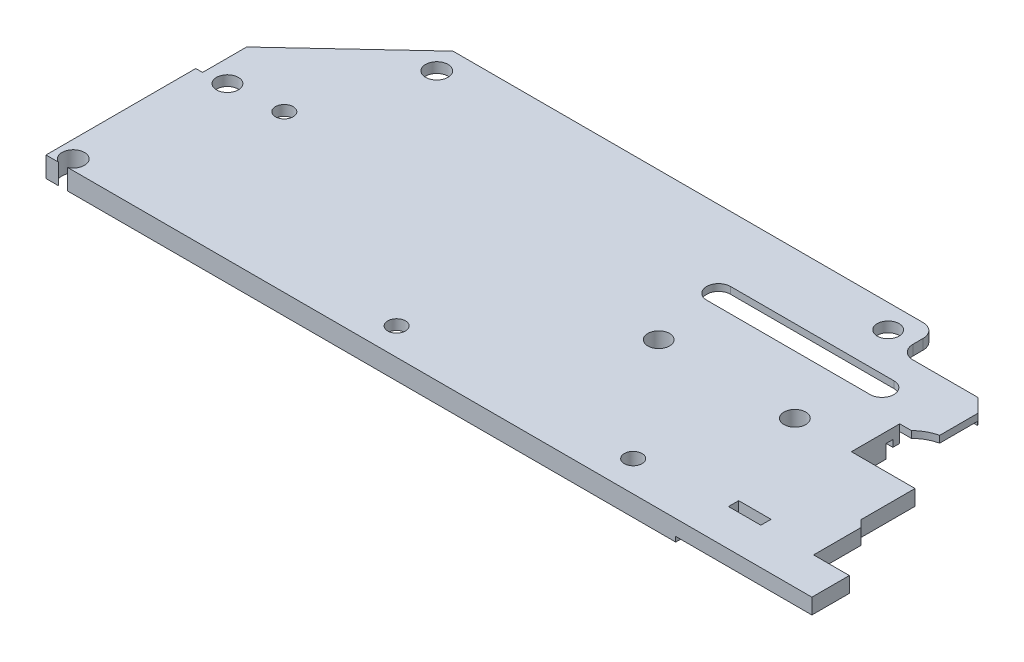
SolidWorks part; units mm, degrees
ref_plane "前视基准面" through (0, 0, 0) normal (0, 0, 1) x (1, 0, 0)
ref_plane "上视基准面" through (0, 0, 0) normal (0, 1, 0) x (1, 0, 0)
ref_plane "右视基准面" through (0, 0, 0) normal (1, 0, 0) x (0, 0, -1)
other "Configuration Table"
sketch "草图1" plane through (0, 0, 0) normal (0, 1, 0) x (1, 0, 0)
  line L0 (0, 0) -> (20, 0) construction
  line L2 (-3, 5) -> (27.5, 5)
  line L3 (-3, 5) -> (-3, -3.5)
  line L4 (-3, -3.5) -> (27.5, -3.5)
  line L5 (27.5, 5) -> (27.5, -3.5)
  line L6 (-3, 5) -> (27.5, -3.5) construction
  line L7 (-3, -3.5) -> (27.5, 5) construction
  circle A0 centre (0, 0) radius 1.6
  circle A1 centre (20, 0) radius 1.6
  point P9 (12.25, 0.75)
  dimension "D1" = 20
  dimension "D2" = 3.2
  dimension "D3" = 3
  dimension "D4" = 3.5
  dimension "D5" = 5
  dimension "D6" = 30.5
extrude "凸台-拉伸1" add sketch "草图1" along normal blind 3.5
sketch "草图2" plane through (0, 3.5, 0) normal (0, 1, 0) x (1, 0, 0)
  line L1 (-3, -3.5) -> (27.5, -3.5)
  line L2 (-3, -3.5) -> (-3, -21.5)
  line L3 (-3, -21.5) -> (27.5, -21.5)
  line L4 (27.5, -3.5) -> (27.5, -21.5)
  line L5 (-3, -3.5) -> (27.5, -21.5) construction
  line L6 (-3, -21.5) -> (27.5, -3.5) construction
  point P4 (12.25, -12.5)
  dimension "D1" = 18
extrude "凸台-拉伸2" add sketch "草图2" against normal blind 3
sketch "草图3" plane through (0, 3.5, 0) normal (0, 1, 0) x (1, 0, 0)
  line L1 (-3, 5) -> (27.5, 5)
  line L2 (-3, 5) -> (-3, 21.6)
  line L3 (-3, 21.6) -> (27.5, 21.6)
  line L4 (27.5, 5) -> (27.5, 21.6)
  line L5 (-3, 5) -> (27.5, 21.6) construction
  line L6 (-3, 21.6) -> (27.5, 5) construction
  point P4 (12.25, 13.3)
  dimension "D1" = 16.6
extrude "凸台-拉伸3" add sketch "草图3" against normal blind 1.5
sketch "草图4" plane through (-3, 0, 0) normal (-1, 0, 0) x (0, 0, 1)
  line L0 (3.5, 0.5) -> (-5, 0.5)
  line L1 (3.5, 0.5) -> (3.5, 0) construction
  line L2 (-5, 2) -> (-5, 0) construction
  line L3 (-5, 0.5) -> (-5, 2)
  line L8 (-5, 0) -> (3.5, 0)
  line L9 (3.5, 0) -> (3.5, 0.5)
  line L10 (3.5, 0.5) -> (21.5, 0.5)
  line L11 (21.5, 0.5) -> (21.5, 3.5)
  line L12 (21.5, 3.5) -> (-21.6, 3.5)
  line L13 (-21.6, 3.5) -> (-21.6, 2)
  line L14 (-21.6, 2) -> (-5, 2)
  line L15 (-5, 2) -> (-5, 0)
  line L18 (3.5, 0.5) -> (21.5, 0.5)
  line L19 (21.5, 0.5) -> (21.5, 3.5)
  line L20 (21.5, 3.5) -> (-21.6, 3.5)
  line L21 (-21.6, 3.5) -> (-21.6, 2)
  line L22 (-21.6, 2) -> (-5, 2)
  dimension "D1" = 0
extrude "凸台-拉伸4" add sketch "草图4" along normal blind 57
sketch "草图5" plane through (-60, 0, 0) normal (-1, 0, 0) x (0, 0, 1)
  line L1 (-21.6, 2) -> (21.5, 2)
  line L2 (-21.6, 2) -> (-21.6, 3.5)
  line L3 (-21.6, 3.5) -> (21.5, 3.5)
  line L4 (21.5, 2) -> (21.5, 3.5)
  line L5 (-21.6, 2) -> (21.5, 3.5) construction
  line L6 (-21.6, 3.5) -> (21.5, 2) construction
  point P4 (-0.05, 2.75)
extrude "凸台-拉伸5" add sketch "草图5" along normal blind 2.5
sketch "草图6" plane through (0, 3.5, 0) normal (0, 1, 0) x (1, 0, 0)
  line L0 (-53.5761, 21.6) -> (-62.5, 13.2783)
  line L1 (-62.5, -21.5) -> (-62.5, 21.6) construction
  line L2 (-62.5, 13.2783) -> (-62.5, 21.6)
  line L3 (-62.5, 21.6) -> (-53.5761, 21.6)
  line L7 (27.5, 21.6) -> (-62.5, 21.6) construction
  dimension "D1" = 8.9239
  dimension "D2" = 8.3217
extrude "切除-拉伸1" cut sketch "草图6" against normal through all
sketch "草图7" plane through (0, 0.5, 0) normal (0, -1, 0) x (1, 0, 0)
  line L0 (-3, -5) -> (-3, 3.5) construction
  line L1 (-60, -5) -> (-3, -5)
  line L2 (-60, -5) -> (-60, -4)
  line L3 (-60, -4) -> (-3, -4)
  line L4 (-3, -5) -> (-3, -4)
  line L5 (-60, -5) -> (-3, -4) construction
  line L6 (-60, -4) -> (-3, -5) construction
  point P4 (-31.5, -4.5)
  dimension "D1" = 1
extrude "切除-拉伸2" cut sketch "草图7" against normal up to surface (1.5 mm away) up to face at (-34.7966, 2, -3.354)
sketch "草图8" plane through (27.5, 0, 0) normal (1, 0, 0) x (0, 0, -1)
  line L1 (-3.5, 0.5) -> (-21.5, 0.5)
  line L2 (-3.5, 0.5) -> (-3.5, 3.5)
  line L3 (-3.5, 3.5) -> (-21.5, 3.5)
  line L4 (-21.5, 0.5) -> (-21.5, 3.5)
  line L5 (-3.5, 0.5) -> (-21.5, 3.5) construction
  line L6 (-3.5, 3.5) -> (-21.5, 0.5) construction
  point P4 (-12.5, 2)
extrude "凸台-拉伸6" add sketch "草图8" along normal blind 16.5
sketch "草图9" plane through (0, 0.5, 0) normal (0, -1, 0) x (1, 0, 0)
  line L1 (44, 21.5) -> (24, 21.5)
  line L2 (44, 21.5) -> (44, 11.1)
  line L3 (44, 11.1) -> (24, 11.1)
  line L4 (24, 21.5) -> (24, 11.1)
  line L5 (44, 21.5) -> (24, 11.1) construction
  line L6 (44, 11.1) -> (24, 21.5) construction
  point P4 (34, 16.3)
  dimension "D1" = 20
  dimension "D2" = 10.4
extrude "切除-拉伸3" cut sketch "草图9" against normal blind 0.725 contours L4 L3 L2 L1
sketch "草图10" plane through (0, 1.225, 0) normal (0, -1, 0) x (1, 0, 0)
  line L0 (44, 21.5) -> (24, 21.5) construction
  line L1 (26.35, 16.1) -> (31.1, 16.1)
  line L2 (26.35, 16.1) -> (26.35, 14.6)
  line L3 (26.35, 14.6) -> (31.1, 14.6)
  line L4 (31.1, 16.1) -> (31.1, 14.6)
  line L5 (26.35, 16.1) -> (31.1, 14.6) construction
  line L6 (26.35, 14.6) -> (31.1, 16.1) construction
  line L8 (44, 21.5) -> (44, 11.1) construction
  point P4 (28.725, 15.35)
  dimension "D1" = 4.75
  dimension "D2" = 1.5
  dimension "D3" = 5.4
  dimension "D4" = 17.65
extrude "切除-拉伸4" cut sketch "草图10" against normal up to next
sketch "草图11" plane through (0, 0.5, 0) normal (0, -1, 0) x (1, 0, 0)
  line L0 (44, 11.1) -> (24, 11.1) construction
  line L1 (44, 3.5) -> (29, 3.5)
  line L2 (44, 3.5) -> (44, 11.1)
  line L3 (44, 11.1) -> (29, 11.1)
  line L4 (29, 3.5) -> (29, 11.1)
  line L5 (44, 3.5) -> (29, 11.1) construction
  line L6 (44, 11.1) -> (29, 3.5) construction
  line L7 (24, 21.5) -> (24, 11.1) construction
  point P4 (36.5, 7.3)
  dimension "D1" = 5
extrude "切除-拉伸5" cut sketch "草图11" against normal up to surface (0.725 mm away) up to face at (28.725, 1.225, 15.35)
sketch "草图12" plane through (27.5, 0, 0) normal (1, 0, 0) x (0, 0, -1)
  line L1 (5, 0) -> (-3.5, 0)
  line L2 (5, 0) -> (5, 3.5)
  line L3 (5, 3.5) -> (-3.5, 3.5)
  line L4 (-3.5, 0) -> (-3.5, 3.5)
  line L5 (5, 0) -> (-3.5, 3.5) construction
  line L6 (5, 3.5) -> (-3.5, 0) construction
  point P4 (0.75, 1.75)
extrude "凸台-拉伸7" add sketch "草图12" along normal up to surface (1.5 mm away) up to face at (29, 0.8625, 7.3)
sketch "草图13" plane through (0, 0, 0) normal (0, -1, 0) x (1, 0, 0)
  line L0 (27.5, -5) -> (29, 3.5)
  line L1 (29, 3.5) -> (29, -5)
  line L2 (29, -5) -> (27.5, -5)
extrude "切除-拉伸6" cut sketch "草图13" against normal up to next
sketch "草图14" plane through (0, 3.5, 0) normal (0, 1, 0) x (1, 0, 0)
  line L0 (28.4, -0.1) -> (29, -3.5)
  line L1 (29, -3.5) -> (27.5, 5) construction
  line L2 (29, -3.5) -> (33.5, -3.5)
  line L3 (44, -3.5) -> (29, -3.5) construction
  line L4 (33.5, -3.5) -> (33.5, -0.1)
  line L5 (33.5, -0.1) -> (28.4, -0.1)
  line L6 (44, -3.5) -> (44, -21.5) construction
  dimension "D1" = 10.5
  dimension "D2" = 3.4
extrude "凸台-拉伸8" add sketch "草图14" against normal up to surface (3.5 mm away) up to face at (12.625, 0, -0.75)
sketch "草图15" plane through (0, 3.5, 0) normal (0, 1, 0) x (1, 0, 0)
  line L0 (44, -3.5) -> (44, -21.5) construction
  line L1 (33.5, -3.5) -> (40.5, -3.5)
  line L2 (33.5, -3.5) -> (33.5, -0.1)
  line L3 (33.5, -0.1) -> (40.5, -0.1)
  line L4 (40.5, -3.5) -> (40.5, -0.1)
  line L5 (33.5, -3.5) -> (40.5, -0.1) construction
  line L6 (33.5, -0.1) -> (40.5, -3.5) construction
  point P4 (37, -1.8)
  dimension "D1" = 3.5
extrude "凸台-拉伸9" add sketch "草图15" against normal up to surface (2.275 mm away) up to face at (28.725, 1.225, 15.35)
sketch "草图16" plane through (0, 3.5, 0) normal (0, 1, 0) x (1, 0, 0)
  line L0 (40.5, -3.5) -> (40.5, -0.1) construction
  line L1 (44, -3.5) -> (40.5, -3.5)
  line L2 (44, -3.5) -> (44, -2)
  line L3 (44, -2) -> (40.5, -2)
  line L4 (40.5, -3.5) -> (40.5, -2)
  line L5 (44, -3.5) -> (40.5, -2) construction
  line L6 (44, -2) -> (40.5, -3.5) construction
  point P4 (42.25, -2.75)
  dimension "D1" = 1.5
extrude "凸台-拉伸10" add sketch "草图16" against normal up to surface (2.275 mm away) up to face at (28.725, 1.225, 15.35)
sketch "草图17" plane through (0, 1.225, 0) normal (0, -1, 0) x (1, 0, 0)
  line L0 (44, 21.5) -> (44, 2) construction
  line L1 (44, 16) -> (38.75, 16)
  line L2 (44, 16) -> (44, 0.1)
  line L3 (44, 0.1) -> (38.75, 0.1)
  line L4 (38.75, 16) -> (38.75, 0.1)
  line L5 (44, 16) -> (38.75, 0.1) construction
  line L6 (44, 0.1) -> (38.75, 16) construction
  line L7 (44, 21.5) -> (24, 21.5) construction
  line L8 (40.5, 0.1) -> (33.5, 0.1) construction
  point P4 (41.375, 8.05)
  dimension "D1" = 5.25
  dimension "D2" = 5.5
extrude "切除-拉伸7" cut sketch "草图17" against normal up to next
sketch "草图18" plane through (0, 0.5, 0) normal (0, -1, 0) x (1, 0, 0)
  line L0 (24, 11.1) -> (29, 6.1)
  line L1 (29, 11.1) -> (29, 3.5) construction
  line L2 (29, 6.1) -> (29, 11.1)
  line L3 (29, 11.1) -> (24, 11.1)
extrude "切除-拉伸8" cut sketch "草图18" against normal up to surface (0.725 mm away) up to face at (33.85, 1.225, 10.44)
sketch "草图19" plane through (0, 1.225, 0) normal (0, -1, 0) x (1, 0, 0)
  line L0 (38.75, 9) -> (37.75, 9)
  line L1 (38.75, 16) -> (38.75, 0.1) construction
  line L2 (37.75, 9) -> (37.75, 0.1)
  line L3 (38.75, 0.1) -> (33.5, 0.1) construction
  line L4 (37.75, 0.1) -> (38.75, 0.1)
  line L5 (38.75, 0.1) -> (38.75, 9)
  line L6 (44, 16) -> (38.75, 16) construction
  dimension "D1" = 1
  dimension "D2" = 7
extrude "切除-拉伸9" cut sketch "草图19" against normal up to next
chamfer "倒角1" distance 1 angle 45 1 edges at (37.75, 2.3625, 9)
sketch "草图20" plane through (0, 3.5, 0) normal (0, 1, 0) x (1, 0, 0)
  line L0 (-1.5, 10.3) -> (22.5, 10.3) construction
  line L1 (-1.5, 12.05) -> (22.5, 12.05)
  line L2 (-1.5, 8.55) -> (22.5, 8.55)
  line L3 (27.5, 21.6) -> (-53.5761, 21.6) construction
  line L4 (27.5, 5) -> (27.5, 21.6) construction
  arc A0 (-1.5, 12.05) -> (-1.5, 8.55) centre (-1.5, 10.3) ccw
  arc A1 (22.5, 8.55) -> (22.5, 12.05) centre (22.5, 10.3) ccw
  point P2 (10.5, 10.3)
  dimension "D4" = 1.75
  dimension "D1" = 11.3
  dimension "D2" = 24
  dimension "D3" = 17
extrude "切除-拉伸10" cut sketch "草图20" against normal up to next
sketch "草图22" plane through (0, 2, 0) normal (0, -1, 0) x (1, 0, 0)
  line L2 (-51.1362, -18.4059) -> (16.75, -18.4059)
  line L3 (27.5, -5) -> (27.5, -21.6) construction
  line L4 (16.75, -18.4059) -> (16.75, -19.4059)
  line L7 (-59, -6) -> (27.5, -6)
  line L8 (-52.6024, -18.4059) -> (-60, -11.5076)
  line L9 (-51.5301, -19.4059) -> (-60.454, -11.0842)
  line L11 (-51.5301, -19.4059) -> (-52.6024, -18.4059)
  line L14 (16.75, -19.4059) -> (-51.5301, -19.4059)
  line L15 (-60, -11.5076) -> (-60, -6)
  line L16 (-60, -6) -> (-59, -6)
  line L17 (-59, -7) -> (-59, -11.0728)
  line L18 (-59, -11.0728) -> (-51.1362, -18.4059)
  line L20 (-60, -4) -> (-60, 21.5) construction
  line L21 (-60, -4) -> (-3, -4) construction
  line L22 (-59, -7) -> (27.5, -7)
  line L23 (27.5, -6) -> (27.5, -7)
  line L24 (-59, -6) -> (27.5, -7) construction
  line L25 (-59, -7) -> (27.5, -6) construction
  point P19 (-15.75, -6.5)
  dimension "D2" = 1
  dimension "D3" = 1
  dimension "D4" = 2
  dimension "D5" = 1
  dimension "D6" = 1
  dimension "D7" = 10.75
  dimension "D1" = 3
extrude "凸台-拉伸12" add sketch "草图22" along normal blind 1
sketch "草图23" plane through (0, 3.5, 0) normal (0, 1, 0) x (1, 0, 0)
  line L0 (-62.5, -21.5) -> (-62.5, 13.2783) construction
  line L1 (-62.5, -21.5) -> (44, -21.5) construction
  line L2 (-62.5, 13.2783) -> (-67.5, 8.6157)
  line L3 (-67.5, 8.6157) -> (-67.5, -21.5)
  line L4 (-67.5, -21.5) -> (-62.5, -21.5)
  line L5 (-62.5, -21.5) -> (-62.5, 13.2783)
  line L6 (-62.5, 13.2783) -> (-53.5761, 21.6) construction
  circle A0 centre (-64.25, 0.9) radius 1.6
  dimension "D1" = 1.75
  dimension "D3" = 3.2
  dimension "D2" = 22.4
  dimension "D4" = 5
extrude "凸台-拉伸13" add sketch "草图23" against normal up to surface (1.5 mm away) up to face at (10.5, 2, -10.3)
sketch "草图24" plane through (0, 2, 0) normal (0, -1, 0) x (1, 0, 0)
  line L0 (-67.5, -8.6157) -> (-67.5, 21.5) construction
  line L1 (-60, 21.5) -> (-67.5, 21.5)
  line L2 (-60, 21.5) -> (-60, 4.5)
  line L3 (-60, 4.5) -> (-67.5, 4.5)
  line L4 (-67.5, 21.5) -> (-67.5, 4.5)
  line L5 (-60, 21.5) -> (-67.5, 4.5) construction
  line L6 (-60, 4.5) -> (-67.5, 21.5) construction
  point P4 (-63.75, 13)
  dimension "D1" = 17
extrude "凸台-拉伸14" add sketch "草图24" along normal up to surface (1.5 mm away) up to face at (-2.5, 0.5, 7.4)
chamfer "倒角2" distance 4.5 angle 37.5 1 edges at (-60, 1.25, 4.5)
sketch "草图25" plane through (0, 3.5, 0) normal (0, 1, 0) x (1, 0, 0)
  line L0 (27.5, 21.6) -> (-53.5761, 21.6) construction
  line L1 (-67.5, 8.6157) -> (-67.5, -21.5) construction
  circle A0 centre (-50.5, 17.9) radius 1.65
  dimension "D1" = 3.3
  dimension "D2" = 3.7
  dimension "D3" = 17
extrude "切除-拉伸11" cut sketch "草图25" against normal up to next
sketch "草图26" plane through (0, 2, 0) normal (0, -1, 0) x (1, 0, 0)
  circle A0 centre (-50.5, -17.9) radius 4
  dimension "D1" = 8
extrude "切除-拉伸12" cut sketch "草图26" along normal up to next
fillet "圆角1" radius 1 2 edges at (-46.7943, 1.5, -19.4059) (-54.3413, 1.5, -16.7844)
sketch "草图27" plane through (0, 2, 0) normal (0, -1, 0) x (1, 0, 0)
  line L0 (-53.914, -15.8156) -> (-54.6574, -15.1223)
  line L1 (-53.914, -15.8156) -> (-59, -11.0728) construction
  line L2 (-45.5257, -18.4059) -> (-46.5321, -18.4059)
  line L3 (16.75, -18.4059) -> (-46.5321, -18.4059) construction
  arc A0 (-46.5321, -18.4059) -> (-53.914, -15.8156) centre (-50.5, -17.9) ccw
  arc A1 (-45.5257, -18.4059) -> (-54.6574, -15.1223) centre (-50.5, -17.9) ccw
  dimension "D1" = 1
extrude "凸台-拉伸15" add sketch "草图27" along normal up to surface (1 mm away) up to face at (-36.5289, 1, -10.0692)
fillet "圆角2" radius 1 4 edges at (-60, 1.5, -11.5076) (-59, 1.5, -11.0728) (-45.5257, 1.5, -18.4059) (-54.6574, 1.5, -15.1223)
fillet "圆角3" radius 1 3 edges at (-60, 1.25, -4) (-60, 1.5, -6) (-59, 1.5, -7)
sketch "草图28" plane through (0, 2, 0) normal (0, -1, 0) x (1, 0, 0)
  line L1 (27.5, -21.6) -> (20.5, -21.6)
  line L2 (27.5, -21.6) -> (27.5, -17.4)
  line L3 (27.5, -17.4) -> (20.5, -17.4)
  line L4 (20.5, -21.6) -> (20.5, -17.4)
  line L5 (27.5, -21.6) -> (20.5, -17.4) construction
  line L6 (27.5, -17.4) -> (20.5, -21.6) construction
  point P4 (24, -19.5)
  dimension "D1" = 4.2
  dimension "D2" = 7
extrude "切除-拉伸13" cut sketch "草图28" against normal up to next
sketch "草图29" plane through (0, 2, 0) normal (0, -1, 0) x (1, 0, 0)
  line L0 (20.5, -21.6) -> (19.25, -21.6)
  line L1 (20.5, -21.6) -> (-53.5761, -21.6) construction
  line L2 (19.25, -21.6) -> (19.25, -16.1)
  line L3 (19.25, -16.1) -> (27.5, -16.1)
  line L4 (27.5, -7) -> (27.5, -17.4) construction
  line L5 (27.5, -16.1) -> (27.5, -17.4)
  line L6 (27.5, -17.4) -> (20.5, -17.4) construction
  line L7 (27.5, -17.4) -> (20.5, -17.4)
  line L8 (20.5, -17.4) -> (20.5, -21.6)
  dimension "D1" = 1.3
  dimension "D2" = 1.25
extrude "凸台-拉伸16" add sketch "草图29" along normal up to surface (1 mm away) up to face at (-39.2289, 1, -12.6385)
fillet "圆角4" radius 2 2 edges at (19.25, 1.5, -16.1) (20.5, 2.25, -17.4)
sketch "草图30" plane through (0, 2, 0) normal (0, -1, 0) x (1, 0, 0)
  line L0 (19.25, -21.6) -> (-53.5761, -21.6) construction
  line L1 (27.5, -7) -> (27.5, -16.1) construction
  circle A0 centre (15.6, -18.1) radius 1.6
  dimension "D1" = 3.2
  dimension "D2" = 3.5
  dimension "D3" = 11.9
extrude "切除-拉伸14" cut sketch "草图30" against normal up to next
sketch "草图31" plane through (0, 2, 0) normal (0, -1, 0) x (1, 0, 0)
  circle A0 centre (15.6, -18.1) radius 3.75
  dimension "D1" = 7.5
extrude "切除-拉伸15" cut sketch "草图31" along normal up to next
fillet "圆角5" radius 1 1 edges at (12.0847, 1.5, -19.4059)
sketch "草图32" plane through (0, 1, 0) normal (0, -1, 0) x (1, 0, 0)
  line L1 (19.25, -18.9602) -> (19.25, -18.1)
  line L5 (19.25, -18.9602) -> (19.25, -21.6)
  line L6 (20.5, -21.6) -> (20.5, -19.4)
  line L7 (22.5, -17.4) -> (27.5, -17.4)
  line L8 (27.5, -17.4) -> (27.5, -16.1)
  line L9 (27.5, -16.1) -> (21.25, -16.1)
  line L10 (19.25, -18.9602) -> (19.25, -21.6)
  line L11 (20.5, -21.6) -> (20.5, -19.4)
  line L12 (22.5, -17.4) -> (27.5, -17.4)
  line L13 (27.5, -17.4) -> (27.5, -16.1)
  line L14 (27.5, -16.1) -> (21.25, -16.1)
  line L16 (19.25, -21.6) -> (20.5, -21.6)
  line L17 (19.25, -21.6) -> (20.5, -21.6)
  arc A3 (19.25, -18.9602) -> (19.3155, -17.5924) centre (15.6, -18.1) ccw
  arc A4 (22.5, -17.4) -> (20.5, -19.4) centre (22.5, -19.4) ccw
  arc A5 (21.25, -16.1) -> (19.3155, -17.5924) centre (21.25, -18.1) ccw
  arc A7 (22.5, -17.4) -> (20.5, -19.4) centre (22.5, -19.4) ccw
  arc A8 (21.25, -16.1) -> (19.25, -18.1) centre (21.25, -18.1) ccw
  dimension "D1" = 0
extrude "切除-拉伸16" cut sketch "草图32" against normal up to next
fillet "圆角7" radius 2 1 edges at (19.25, 2.75, -21.6)
sketch "草图33" plane through (0, 0, 0) normal (0, -1, 0) x (1, 0, 0)
  line L0 (28.4, 0.1) -> (27.5, -5)
  line L1 (27.5, -5) -> (28.4, -5)
  line L2 (28.4, -5) -> (28.4, 0.1)
extrude "凸台-拉伸17" add sketch "草图33" against normal up to surface (3.5 mm away) up to face at (13.3015, 3.5, -2.1572)
sketch "草图34" plane through (27.5, 0, 0) normal (1, 0, 0) x (0, 0, -1)
  line L8 (7, 2) -> (16.1, 2)
  line L9 (16.1, 2) -> (16.1, 3.5)
  line L10 (16.1, 3.5) -> (5, 3.5)
  line L11 (5, 3.5) -> (5, 2)
  line L12 (5, 2) -> (6, 2)
  line L13 (6, 2) -> (6, 1)
  line L14 (6, 1) -> (7, 1)
  line L15 (7, 1) -> (7, 2)
  line L16 (7, 2) -> (16.1, 2)
  line L17 (16.1, 2) -> (16.1, 3.5)
  line L18 (16.1, 3.5) -> (5, 3.5)
  line L19 (5, 3.5) -> (5, 2)
  line L20 (5, 2) -> (6, 2)
  line L21 (6, 2) -> (6, 1)
  line L22 (6, 1) -> (7, 1)
  line L23 (7, 1) -> (7, 2)
  dimension "D1" = 0
extrude "凸台-拉伸18" add sketch "草图34" along normal up to surface (0.9 mm away) up to face at (28.4, 1.75, -2.45)
sketch "草图35" plane through (0, 2, 0) normal (0, -1, 0) x (1, 0, 0)
  line L1 (28.4, -7) -> (-8.6, -7)
  line L2 (28.4, -7) -> (28.4, -14)
  line L3 (28.4, -14) -> (-8.6, -14)
  line L4 (-8.6, -7) -> (-8.6, -14)
  line L5 (28.4, -7) -> (-8.6, -14) construction
  line L6 (28.4, -14) -> (-8.6, -7) construction
  point P4 (9.9, -10.5)
  dimension "D1" = 7
  dimension "D2" = 37
extrude "切除-拉伸17" cut sketch "草图35" against normal blind 0.5
chamfer "倒角3" distance 0.5 angle 45 1 edges at (-8.6, 2, -10.5)
sketch "草图36" plane through (28.4, 0, 0) normal (1, 0, 0) x (0, 0, -1)
  line L0 (16.1, 2) -> (16.1, 3.5)
  line L1 (16.1, 3.5) -> (7, 3.5)
  line L2 (16.1, 3.5) -> (-0.1, 3.5) construction
  line L3 (7, 3.5) -> (7, 2.5)
  line L4 (14, 2.5) -> (7, 2.5) construction
  line L5 (7, 2.5) -> (14, 2.5)
  line L6 (14, 2.5) -> (14, 2)
  line L7 (14, 2) -> (16.1, 2)
extrude "凸台-拉伸19" add sketch "草图36" along normal blind 4.4
sketch "草图37" plane through (0, 3.5, 0) normal (0, 1, 0) x (1, 0, 0)
  line L0 (32.8, 16.1) -> (21.25, 16.1) construction
  line L1 (32.8, 16.1) -> (32.8, 7) construction
  line L2 (32.8, 7) -> (28.4, 7) construction
  line L3 (30.1219, 7) -> (32.8, 7)
  line L4 (32.8, 7) -> (32.8, 8.4675)
  arc A3 (32.8, 8.4675) -> (30.1219, 7) centre (34, 3.1) ccw
  dimension "D1" = 13
  dimension "D2" = 1.2
  dimension "D3" = 5.5
extrude "切除-拉伸18" cut sketch "草图37" against normal through all
sketch "草图38" plane through (0, 3.5, 0) normal (0, 1, 0) x (1, 0, 0)
  circle A0 centre (13.25, -17) radius 1.3
  circle A1 centre (20, 0) radius 1.6 construction
  dimension "D1" = 17
  dimension "D2" = 6.75
  dimension "D3" = 2.6
extrude "切除-拉伸19" cut sketch "草图38" against normal up to next
sketch "草图39" plane through (0, 2, 0) normal (0, -1, 0) x (1, 0, 0)
  line L0 (-67.5, 21.5) -> (24, 21.5) construction
  line L1 (12.8049, -15.6) -> (-46.7437, -15.6)
  line L3 (14.2537, -14.6) -> (-46.7437, -14.6)
  line L4 (-46.7437, -15.6) -> (-46.7437, -14.6)
  line L5 (12.8049, -15.6) -> (-46.7437, -14.6) construction
  line L6 (14.2537, -14.6) -> (-46.7437, -15.6) construction
  circle A0 centre (15.6, -18.1) radius 3.75 construction
  arc A1 (12.8049, -15.6) -> (14.2537, -14.6) centre (15.6, -18.1) cw
  arc A2 (-45.517, -17.4883) -> (-54.0434, -14.3723) centre (-50.5, -17.9) ccw construction
  point P4 (-16.6115, -15.106)
  dimension "D1" = 36.1
  dimension "D2" = 1
extrude "凸台-拉伸20" add sketch "草图39" along normal up to surface (1 mm away) up to face at (-39.6673, 1, -12.6488)
sketch "草图40" plane through (0, 2, 0) normal (0, -1, 0) x (1, 0, 0)
  line L0 (11.5611, -15.6) -> (12.8049, -15.6)
  line L1 (-46.0604, -15.6) -> (12.8049, -15.6) construction
  line L2 (11.8625, -18.4059) -> (10.8599, -18.4059)
  arc A0 (12.8049, -15.6) -> (11.8625, -18.4059) centre (15.6, -18.1) ccw
  arc A1 (11.5611, -15.6) -> (10.8599, -18.4059) centre (15.6, -18.1) ccw
  dimension "D1" = 1
extrude "凸台-拉伸21" add sketch "草图40" along normal up to surface (1 mm away) up to face at (-35.8335, 1, -13.1002)
fillet "圆角8" radius 1 2 edges at (11.5611, 1.5, -15.6) (10.8599, 1.5, -18.4059)
fillet "圆角9" radius 1 1 edges at (14.2537, 1.5, -14.6)
fillet "圆角10" radius 1 2 edges at (-46.0604, 1.5, -15.6) (-46.7437, 1.5, -14.6)
sketch "草图41" plane through (0, 3.5, 0) normal (0, 1, 0) x (1, 0, 0)
  line L1 (-67.5, -21.5) -> (-68.5, -21.5)
  line L2 (-67.5, -21.5) -> (-67.5, 0.5)
  line L3 (-67.5, 0.5) -> (-68.5, 0.5)
  line L4 (-68.5, -21.5) -> (-68.5, 0.5)
  line L5 (-67.5, -21.5) -> (-68.5, 0.5) construction
  line L6 (-67.5, 0.5) -> (-68.5, -21.5) construction
  point P4 (-68, -10.5)
  dimension "D1" = 1
  dimension "D2" = 22
extrude "凸台-拉伸22" add sketch "草图41" against normal up to surface (1.5 mm away) up to face at (15.6, 2, -19.7)
sketch "草图42" plane through (0, 0.5, 0) normal (0, -1, 0) x (1, 0, 0)
  line L0 (-67.5, 4.5) -> (-67.5, 3)
  line L1 (-67.5, 3) -> (-62.5452, 3)
  line L2 (-60, 1.047) -> (-64.5, 4.5) construction
  line L3 (-62.5452, 3) -> (-64.5, 4.5)
  line L4 (-64.5, 4.5) -> (-67.5, 4.5)
  dimension "D1" = 1.5
extrude "凸台-拉伸23" add sketch "草图42" against normal up to next
sketch "草图43" plane through (0, 3.5, 0) normal (0, 1, 0) x (1, 0, 0)
  line L0 (-68.5, -21.5) -> (44, -21.5) construction
  line L1 (-68.5, 0.5) -> (-68.5, -21.5) construction
  circle A0 centre (-66, -20) radius 1.65
  dimension "D1" = 1.5
  dimension "D2" = 2.5
  dimension "D3" = 3.3
extrude "切除-拉伸20" cut sketch "草图43" against normal up to next
sketch "草图44" plane through (0, 2, 0) normal (0, -1, 0) x (1, 0, 0)
  line L0 (-68.5, -0.5) -> (-68.5, 21.5) construction
  line L1 (-67.5, 21.5) -> (-68.5, 21.5)
  line L2 (-67.5, 21.5) -> (-67.5, 20.6874)
  line L3 (-67.5, 18) -> (-68.5, 18)
  line L4 (-68.5, 21.5) -> (-68.5, 18)
  line L5 (-67.5, 21.5) -> (-68.5, 18) construction
  line L6 (-67.5, 18) -> (-68.5, 21.5) construction
  line L7 (-67.5, 19.3126) -> (-67.5, 18)
  arc A0 (-67.5, 19.3126) -> (-65.3126, 21.5) centre (-66, 20) ccw construction
  arc A1 (-67.5, 20.6874) -> (-67.5, 19.3126) centre (-66, 20) ccw construction
  arc A2 (-67.5, 20.6874) -> (-67.5, 19.3126) centre (-66, 20) ccw
  point P4 (-68, 19.75)
  dimension "D1" = 2
extrude "凸台-拉伸24" add sketch "草图44" along normal up to surface (1.5 mm away) up to face at (13.25, 0.5, 18.3)
fillet "圆角11" radius 1 1 edges at (-67.5, 1.25, 18)
chamfer "倒角4" distance 2 angle 45 1 edges at (32.8, 2.75, -16.1)
sketch "草图45" plane through (0, 2, 0) normal (0, -1, 0) x (1, 0, 0)
  line L1 (-67.5, -8.6157) -> (-53.5761, -21.6)
  line L2 (-52.7577, -20.7224) -> (-66.6816, -7.7381)
  line L3 (-52.7577, -20.7224) -> (-66.6816, -7.7381)
  line L4 (-53.5761, -21.6) -> (-51.8165, -21.6)
  line L5 (17.25, -21.6) -> (-53.5761, -21.6) construction
  line L6 (-51.8165, -21.6) -> (-52.7577, -20.7224)
  line L7 (-66.6816, -7.7381) -> (-67.5, -6.9749)
  line L8 (-67.5, -8.6157) -> (-67.5, -0.5) construction
  line L9 (-67.5, -6.9749) -> (-67.5, -8.6157)
  dimension "D1" = 1.2
extrude "切除-拉伸21" cut sketch "草图45" against normal up to next
sketch "草图46" plane through (0, 0.5, 0) normal (0, -1, 0) x (1, 0, 0)
  line L0 (-65.3126, 21.5) -> (24, 21.5) construction
  line L1 (-68.5, -0.5) -> (-68.5, 18) construction
  circle A0 centre (-56.5, -1.5) radius 1.3
  circle A1 centre (-21, 17.5) radius 1.3
  point P4 (0, 0)
  point P5 (-13.8932, 18.195)
  dimension "D1" = 35.5
  dimension "D2" = 19
  dimension "D3" = 2.6
  dimension "D4" = 4
  dimension "D5" = 12
extrude "切除-拉伸22" cut sketch "草图46" against normal up to next
sketch "草图47" plane through (0, 0.5, 0) normal (0, -1, 0) x (1, 0, 0)
  line L0 (-60, -3) -> (-60, 1.047) construction
  line L1 (-60, -3) -> (-60, -0.6574)
  arc A0 (-59.0947, -3.9955) -> (-60, -0.6574) centre (-56.5, -1.5) ccw
  circle A1 centre (-21, 17.5) radius 3.6
  arc A2 (-60, -3) -> (-59, -4) centre (-59, -3) ccw construction
  arc A3 (-60, -3) -> (-59.0947, -3.9955) centre (-59, -3) ccw
  dimension "D1" = 7.2
extrude "切除-拉伸24" cut sketch "草图47" against normal blind 1.5
